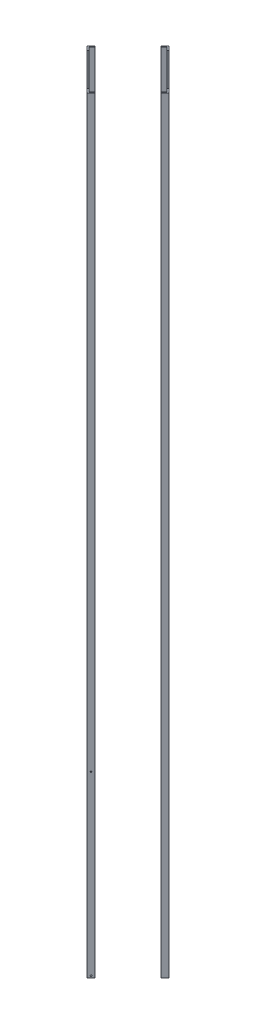
SolidWorks part; units mm, degrees
material "6061-T6 (SS)"
ref_plane "Front Plane" through (0, 0, 0) normal (0, 0, 1) x (1, 0, 0)
ref_plane "Top Plane" through (0, 0, 0) normal (0, 1, 0) x (1, 0, 0)
ref_plane "Right Plane" through (0, 0, 0) normal (1, 0, 0) x (0, 0, -1)
sketch "Sketch2" plane through (0, 0, 0) normal (0, 1, 0) x (1, 0, 0)
  line L0 (0, 94.7743) -> (-8.9803, 85.794)
  line L1 (-8.9803, 85.794) -> (-6.7352, 83.549)
  line L2 (-6.7352, 83.549) -> (0, 90.2842)
  line L3 (0, 90.2842) -> (6.7352, 83.549)
  line L4 (6.7352, 83.549) -> (8.9803, 85.794)
  line L5 (8.9803, 85.794) -> (0, 94.7743)
  line L6 (0, 0) -> (0, 186.644) construction
  line L7 (94.7417, 0.0326) -> (85.7614, 9.0128)
  line L8 (85.7614, 9.0128) -> (83.5164, 6.7678)
  line L9 (83.5164, 6.7678) -> (90.2516, 0.0326)
  line L10 (90.2516, 0.0326) -> (83.5164, -6.7026)
  line L11 (83.5164, -6.7026) -> (85.7614, -8.9477)
  line L12 (85.7614, -8.9477) -> (94.7417, 0.0326)
  line L13 (0, -94.7091) -> (8.9803, -85.7289)
  line L14 (8.9803, -85.7289) -> (6.7352, -83.4838)
  line L15 (6.7352, -83.4838) -> (0, -90.219)
  line L16 (0, -90.219) -> (-6.7352, -83.4838)
  line L17 (-6.7352, -83.4838) -> (-8.9803, -85.7289)
  line L18 (-8.9803, -85.7289) -> (0, -94.7091)
  line L19 (-94.7417, 0.0326) -> (-85.7614, -8.9477)
  line L20 (-85.7614, -8.9477) -> (-83.5164, -6.7026)
  line L21 (-83.5164, -6.7026) -> (-90.2516, 0.0326)
  line L22 (-90.2516, 0.0326) -> (-83.5164, 6.7678)
  line L23 (-83.5164, 6.7678) -> (-85.7614, 9.0128)
  line L24 (-85.7614, 9.0128) -> (-94.7417, 0.0326)
  point P1 (-3.3676, 86.9166)
  point P31 (0, 0.0326)
  dimension "D1" = 127.635
  dimension "D2" = 12.7
  dimension "D3" = 12.7
  dimension "D4" = 3.175
  dimension "D5" = 3.175
  dimension "D7" = 127.635
  dimension "D6" = 4
extrude "Boss-Extrude1" add sketch "Sketch2" along normal blind 1778
sketch "Sketch3" plane through (0, 0, 0) normal (0, -1, 0) x (1, 0, 0)
  circle A0 centre (0, 0) radius 94.7417
sketch "Sketch4" plane through (-47.3546, 0, 47.3546) normal (-0.7071, 0, 0.7071) x (0.7071, 0, 0.7071)
  line L0 (-54.3155, 0) -> (-54.3155, 4.7625)
  line L1 (-54.3155, 1778) -> (-54.3155, 0) construction
  line L2 (-54.3155, 4.7625) -> (-67.0155, 4.7625)
  line L3 (-67.0155, 1778) -> (-67.0155, 0) construction
  circle A0 centre (-60.6655, 4.7625) radius 1.4605
  dimension "D2" = 2.921
  dimension "D1" = 4.7625
extrude "Cut-Extrude1" cut sketch "Sketch4" against normal up to next (3.175 mm away) contours L2 A0 | L2 A0 region at (-90.2516, 4.1426, 4.4575) region at (-90.2516, 5.3824, 4.4575)
sketch "Sketch5" plane through (-47.3871, 0, -47.3871) normal (-0.7071, 0, -0.7071) x (-0.7071, 0, 0.7071)
  line L0 (-54.3155, 1778) -> (-54.3155, 0) construction
  line L1 (-67.0155, 0) -> (-54.3155, 0)
  line L2 (-67.0155, 0) -> (-67.0155, 4.7625)
  line L3 (-67.0155, 4.7625) -> (-54.3155, 4.7625)
  line L4 (-54.3155, 0) -> (-54.3155, 4.7625)
  circle A0 centre (-60.6655, 4.7625) radius 1.4605
  dimension "D2" = 2.921
  dimension "D1" = 4.7625
extrude "Cut-Extrude2" cut sketch "Sketch5" against normal up to next (3.175 mm away) contours L3 A0 | L3 A0 region at (-4.4901, 5.3824, -90.2842) region at (-4.4901, 4.1426, -90.2842)
sketch "Sketch6" plane through (47.3871, 0, -47.3871) normal (0.7071, 0, -0.7071) x (-0.7071, 0, -0.7071)
  line L0 (-54.2695, 1778) -> (-54.2695, 0) construction
  line L1 (-66.9695, 0) -> (-54.2695, 0)
  line L2 (-66.9695, 0) -> (-66.9695, 4.7625)
  line L3 (-66.9695, 4.7625) -> (-54.2695, 4.7625)
  line L4 (-54.2695, 0) -> (-54.2695, 4.7625)
  circle A0 centre (-60.6195, 4.7625) radius 1.4605
  dimension "D2" = 2.921
  dimension "D1" = 4.7625
extrude "Cut-Extrude3" cut sketch "Sketch6" against normal up to next (3.175 mm away) contours L3 A0 | L3 A0 region at (90.2516, 5.3824, -4.5227) region at (90.2516, 4.1426, -4.5227)
sketch "Sketch7" plane through (47.3546, 0, 47.3546) normal (0.7071, 0, 0.7071) x (0.7071, 0, -0.7071)
  line L0 (-54.2695, 1778) -> (-54.2695, 0) construction
  line L1 (-66.9695, 0) -> (-54.2695, 0)
  line L2 (-66.9695, 0) -> (-66.9695, 4.7625)
  line L3 (-66.9695, 4.7625) -> (-54.2695, 4.7625)
  line L4 (-54.2695, 0) -> (-54.2695, 4.7625)
  circle A0 centre (-60.6195, 4.7625) radius 1.4605
  dimension "D2" = 2.921
  dimension "D1" = 4.7625
extrude "Cut-Extrude4" cut sketch "Sketch7" against normal up to next (3.175 mm away) contours L3 A0 | L3 A0 region at (4.4901, 5.3824, 90.219) region at (4.4901, 4.1426, 90.219)
pattern_linear "LPattern1" count 2 spacing 409.575 along (0, 1, 0) of "Cut-Extrude4", "Cut-Extrude3", "Cut-Extrude1", "Cut-Extrude2"
